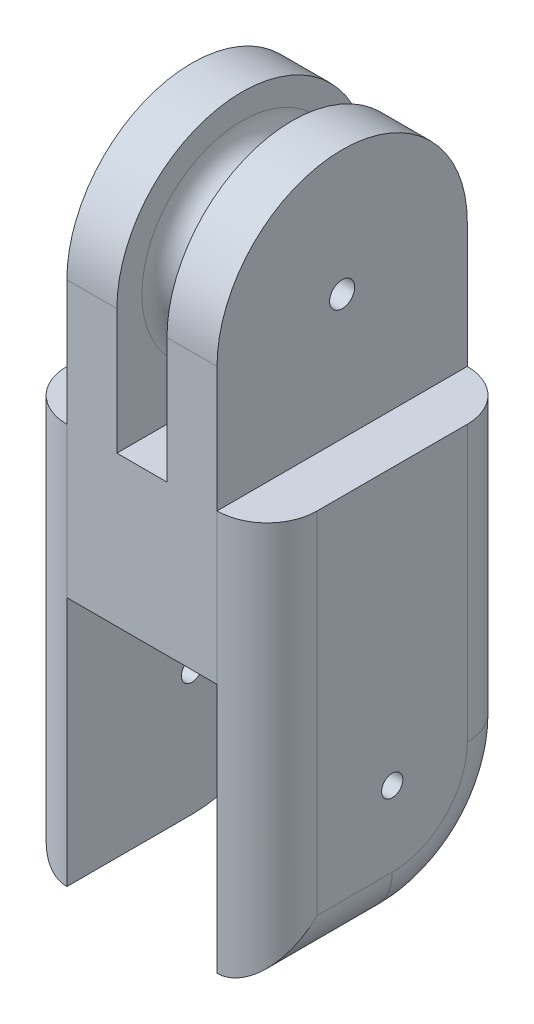
SolidWorks part; units mm, degrees
ref_plane "Front Plane" through (0, 0, 0) normal (0, 0, 1) x (1, 0, 0)
ref_plane "Top Plane" through (0, 0, 0) normal (0, 1, 0) x (1, 0, 0)
ref_plane "Right Plane" through (0, 0, 0) normal (1, 0, 0) x (0, 0, -1)
sketch "Sketch1" plane through (0, 0, 0) normal (0, 1, 0) x (1, 0, 0)
  line L0 (10, 10) -> (-10, -10) construction
  line L1 (-10, 10) -> (10, 10)
  line L2 (-10, 10) -> (-10, -10)
  line L3 (-10, -10) -> (10, -10)
  line L4 (10, 10) -> (10, -10)
  line L5 (-10, 10) -> (10, -10) construction
  point P5 (0, 0)
  dimension "D1" = 20
  dimension "D2" = 20
extrude "Boss-Extrude1" add sketch "Sketch1" along normal blind 12
sketch "Sketch4" plane through (0, 0, 0) normal (0, -1, 0) x (1, 0, 0)
  line L0 (10, -10) -> (-10, -10) construction
  line L1 (-10, 10) -> (-6, 10)
  line L2 (-10, 10) -> (-10, -10)
  line L3 (-10, -10) -> (-6, -10)
  line L4 (-6, 10) -> (-6, -10)
  line L5 (-10, 10) -> (10, 10) construction
  line L6 (10, -10) -> (6, -10)
  line L7 (10, -10) -> (10, 10)
  line L8 (10, 10) -> (6, 10)
  line L9 (6, -10) -> (6, 10)
  dimension "D1" = 4
  dimension "D2" = 4
extrude "Boss-Extrude2" add sketch "Sketch4" along normal blind 10
sketch "Sketch5" plane through (-10, 0, 0) normal (-1, 0, 0) x (0, 0, 1)
  line L0 (10, -10) -> (-10, -10) construction
  line L4 (0, -20) -> (10, -20)
  line L5 (10, -10) -> (10, -20)
  arc A0 (10, -10) -> (0, -20) centre (0, -10) ccw
extrude "Boss-Extrude3" add sketch "Sketch5" against normal blind 4
sketch "Sketch6" plane through (10, 0, 0) normal (1, 0, 0) x (0, 0, -1)
  line L0 (10, -10) -> (-10, -10) construction
  line L4 (0, -20) -> (-10, -20)
  line L5 (-10, -10) -> (-10, -20)
  arc A0 (0, -20) -> (-10, -10) centre (0, -10) ccw
extrude "Boss-Extrude4" add sketch "Sketch6" against normal blind 4
sketch "Sketch7" plane through (-10, 0, 0) normal (-1, 0, 0) x (0, 0, 1)
  circle A0 centre (0, -10) radius 0.85
  dimension "D1" = 1.7
extrude "Cut-Extrude1" cut sketch "Sketch7" against normal through all
fillet "Fillet1" radius 4 8 edges at (-10, -4, 10) (-10, -17.0711, -7.0711) (10, -4, 10) (10, -17.0711, -7.0711) (-10, 1, -10) (10, 1, -10) (10, -20, 5) (-10, -20, 5)
sketch "Sketch8" plane through (0, 12, 0) normal (0, 1, 0) x (1, 0, 0)
  line L0 (6, 10) -> (-6, 10) construction
  line L1 (6, -10) -> (2, -10)
  line L2 (6, -10) -> (6, 10)
  line L3 (6, 10) -> (2, 10)
  line L4 (2, -10) -> (2, 10)
  line L5 (-10, 6) -> (-10, -6) construction
  line L6 (-6, -10) -> (-2, -10)
  line L7 (-6, -10) -> (-6, 10)
  line L8 (-6, 10) -> (-2, 10)
  line L9 (-2, -10) -> (-2, 10)
  line L10 (10, -6) -> (10, 6) construction
  dimension "D1" = 4
  dimension "D2" = 4
  dimension "D3" = 4
  dimension "D4" = 4
extrude "Boss-Extrude5" add sketch "Sketch8" along normal blind 10
sketch "Sketch9" plane through (6, 0, 0) normal (1, 0, 0) x (0, 0, -1)
  line L0 (-10, 22) -> (10, 22) construction
  circle A0 centre (0, 22) radius 10
extrude "Boss-Extrude6" add sketch "Sketch9" against normal blind 4
sketch "Sketch10" plane through (-6, 0, 0) normal (-1, 0, 0) x (0, 0, 1)
  line L0 (-10, 22) -> (10, 22) construction
  circle A0 centre (0, 22) radius 10
extrude "Boss-Extrude7" add sketch "Sketch10" against normal blind 4
sketch "Sketch12" plane through (-6, 0, 0) normal (-1, 0, 0) x (0, 0, 1)
  circle A0 centre (0, 22) radius 1
  dimension "D1" = 2
extrude "Cut-Extrude2" cut sketch "Sketch12" against normal through all
sketch "Sketch13" plane through (-2, 0, 0) normal (1, 0, 0) x (0, 0, -1)
  circle A0 centre (0, 22) radius 6
  dimension "D1" = 12
sketch "Sketch14" plane through (-2, 0, 0) normal (1, 0, 0) x (0, 0, -1)
  circle A0 centre (0, 22) radius 3.5
  dimension "D1" = 7
extrude "Boss-Extrude8" add sketch "Sketch13" along normal blind 4
extrude "Cut-Extrude3" cut sketch "Sketch14" along normal blind 4
fillet "Fillet2" radius 2 2 edges at (2, 22, -6) (-2, 22, 6)
sketch "Sketch16" plane through (0, 0, 0) normal (0, -1, 0) x (1, 0, 0)
  line L0 (6, -10) -> (-6, -10) construction
  line L1 (-6, 0) -> (6, 0) construction
  line L2 (-6, -10) -> (-6, 10) construction
  line L3 (6, 10) -> (6, -10) construction
  circle A0 centre (0, -6) radius 0.5
  circle A1 centre (0, 6) radius 0.5
  dimension "D1" = 1
  dimension "D2" = 4
extrude "Cut-Extrude4" cut sketch "Sketch16" against normal up to next
